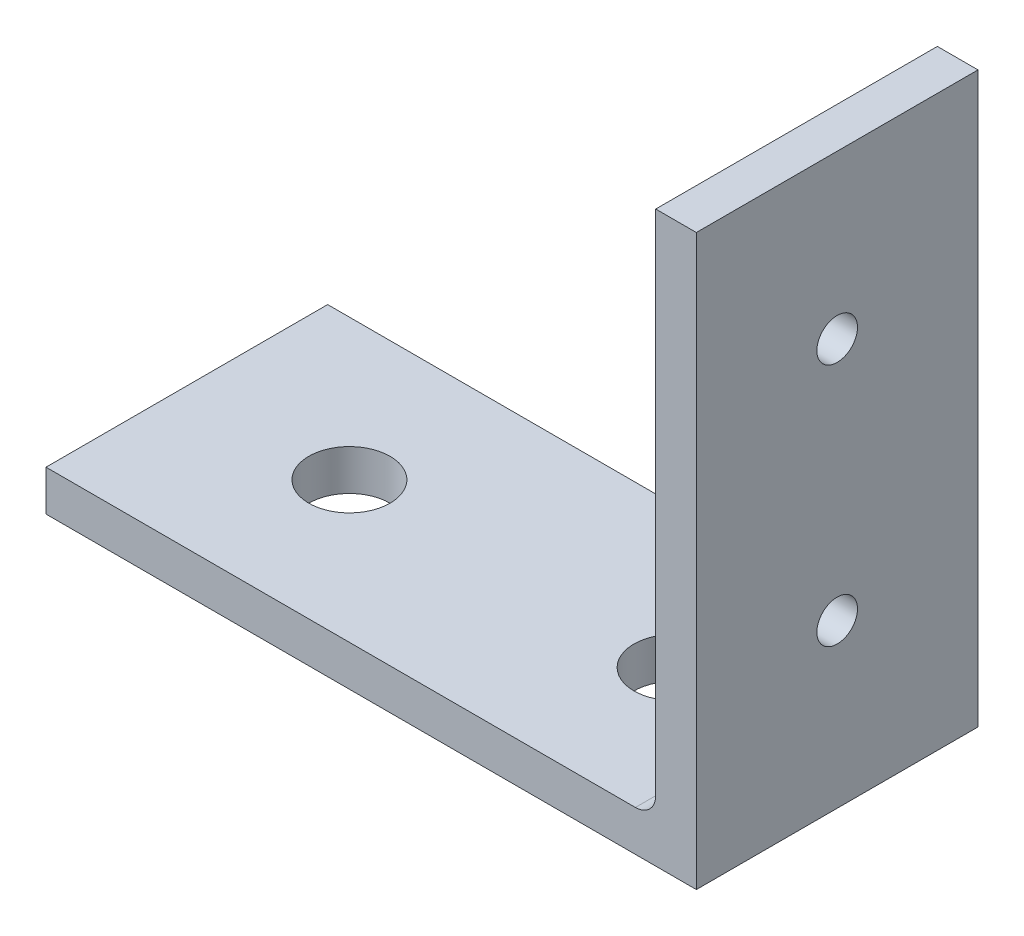
SolidWorks part; units mm, degrees
ref_plane "Front Plane" through (0, 0, 0) normal (0, 0, 1) x (1, 0, 0)
ref_plane "Top Plane" through (0, 0, 0) normal (0, 1, 0) x (1, 0, 0)
ref_plane "Right Plane" through (0, 0, 0) normal (1, 0, 0) x (0, 0, -1)
sketch "Sketch2" plane through (0, 0, 0) normal (0, 0, 1) x (1, 0, 0)
  line L0 (-25.4, 0) -> (25.4, 0)
  line L1 (25.4, 0) -> (25.4, 50.8)
  line L2 (25.4, 50.8) -> (22.225, 50.8)
  line L3 (22.225, 50.8) -> (22.225, 3.175)
  line L4 (22.225, 3.175) -> (-25.4, 3.175)
  line L5 (-25.4, 0) -> (-25.4, 3.175)
  line L6 (23.8125, 50.8) -> (25.4, 50.8) construction
  line L7 (-25.4, 1.5875) -> (-25.4, 0) construction
  dimension "Vert" = 50.8
  dimension "Horz" = 50.8
  dimension "Thickness" = 3.175
extrude "Boss-Extrude1" add sketch "Sketch2" along normal mid plane 22
fillet "Fillet1" radius 1.5875 1 edges at (22.225, 3.175, 0)
ref_plane "Contact Plane 1" through (0, 0, 0) normal (0, -1, 0) x (-1, 0, 0)
ref_plane "Contact Plane 2" through (25.4, 0, 0) normal (1, 0, 0) x (0, 0, -1)
ref_plane "Contact Plane 3" through (0, 3.175, 0) normal (0, 1, 0) x (1, 0, 0)
ref_plane "Contact Plane 4" through (22.225, 0, 0) normal (-1, 0, 0) x (0, 0, 1)
ref_plane "Contact Plane 5" through (0, 0, 11) normal (0, 0, 1) x (1, 0, 0)
ref_plane "Contact Plane 6" through (0, 0, -13.54) normal (0, 0, -1) x (-1, 0, 0)
sketch "Sketch3" plane through (0, 0, 11) normal (0, 0, 1) x (1, 0, 0)
  line L0 (-25.4, 0) -> (25.4, 0) construction
  line L1 (6.0591, 71.0024) -> (30.483, 71.0024)
  line L2 (6.0591, 71.0024) -> (6.0591, 44.45)
  line L3 (6.0591, 44.45) -> (30.483, 44.45)
  line L4 (30.483, 71.0024) -> (30.483, 44.45)
  dimension "D1" = 44.45
extrude "Cut-Extrude1" cut sketch "Sketch3" against normal through all
sketch "Sketch4" plane through (0, 0, 0) normal (0, -1, 0) x (1, 0, 0)
  line L0 (-25.4, 0) -> (-12.7, 0) construction
  line L3 (-25.4, 11) -> (-25.4, -11) construction
  line L4 (-12.7, 0) -> (12.7, 0) construction
  line L5 (12.7, 0) -> (25.4, 0) construction
  line L6 (25.4, 11) -> (25.4, -11) construction
  circle A0 centre (-12.7, 0) radius 3.175
  circle A1 centre (12.7, 0) radius 3.175
  dimension "D1" = 6.35
  dimension "D2" = 12.7
extrude "Cut-Extrude2" cut sketch "Sketch4" against normal through all
sketch "Sketch5" plane through (25.4, 0, 0) normal (1, 0, 0) x (0, 0, -1)
  line L0 (0, 0) -> (0, 12.7) construction
  line L1 (0, 12.7) -> (0, 31.75) construction
  line L2 (0, 31.75) -> (0, 44.45) construction
  line L3 (11, 44.45) -> (-11, 44.45) construction
  circle A0 centre (0, 31.75) radius 1.5875
  circle A1 centre (0, 12.7) radius 1.5875
  dimension "D2" = 3.175
  dimension "D1" = 12.7
extrude "Cut-Extrude3" cut sketch "Sketch5" against normal through all
equation "\"D1@Fillet1\"=\"Thickness@Sketch2\"/2"
